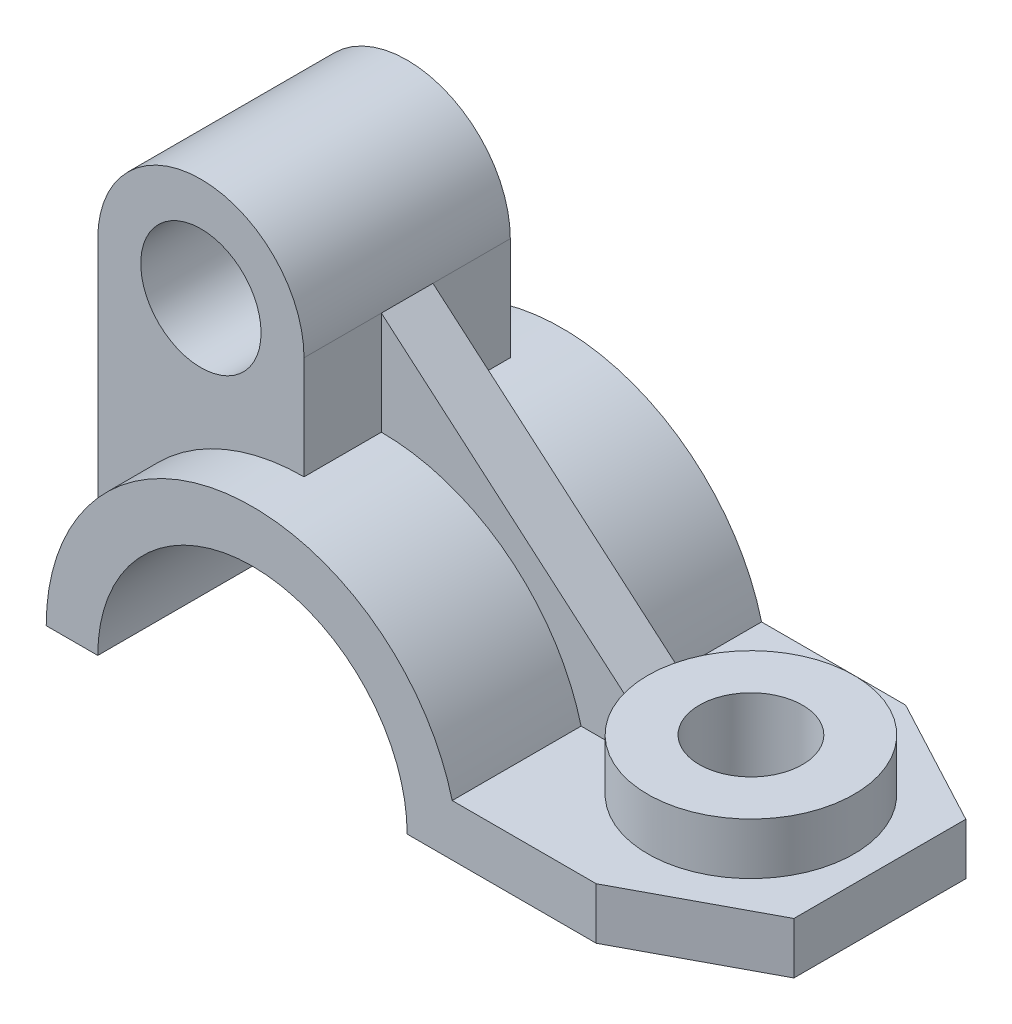
SolidWorks part; units mm, degrees
ref_plane "Front Plane" through (0, 0, 0) normal (0, 0, 1) x (1, 0, 0)
ref_plane "Top Plane" through (0, 0, 0) normal (0, 1, 0) x (1, 0, 0)
ref_plane "Right Plane" through (0, 0, 0) normal (1, 0, 0) x (0, 0, -1)
sketch "Sketch1" plane through (0, 0, 0) normal (0, 0, 1) x (1, 0, 0)
  line L0 (24, 0) -> (55, 0)
  line L1 (55, 0) -> (55, 6)
  line L2 (55, 6) -> (23.2379, 6)
  line L3 (24, 0) -> (18, 0)
  line L4 (-18, 0) -> (-24, 0)
  line L5 (-24, 0) -> (-24, 36)
  line L6 (0, 36) -> (0, 24)
  arc A0 (23.2379, 6) -> (-24, 0) centre (0, 0) ccw
  arc A1 (18, 0) -> (-18, 0) centre (0, 0) ccw
  circle A2 centre (-12, 36) radius 12
  circle A3 centre (-12, 36) radius 7
  dimension "D1" = 36
  dimension "D2" = 48
  dimension "D5" = 36
  dimension "D6" = 24
  dimension "D7" = 14
  dimension "D3" = 55
  dimension "D4" = 6
extrude "Boss-Extrude1" add sketch "Sketch1" along normal mid plane 36 contours A1 L3 L0 L1 L2 A0 L4 region at (21, 0.8257, 0)
extrude "Boss-Extrude2" add sketch "Sketch1<3>" along normal mid plane 24 contours A2 L5 A0 L6 | A2 A3 region at (-16.4261, 21.3196, 0) region at (-12, 47.6606, 0)
sketch "Sketch1<3>" plane through (0, 0, 0) normal (0, 0, 1) x (1, 0, 0) same geometry as "Sketch1"
sketch "Sketch2" plane through (0, 6, 0) normal (0, 1, 0) x (1, 0, 0)
  circle A0 centre (40, 0) radius 12
  dimension "D1" = 24
  dimension "D3" = 40
extrude "Boss-Extrude3" add sketch "Sketch2" along normal blind 6
sketch "Sketch3" plane through (0, 0, 0) normal (0, 0, 1) x (1, 0, 0)
  line L0 (0, 36) -> (28, 12)
  line L1 (0, 36) -> (0, 24) construction
  dimension "D1" = 12
rib "Rib1" sketch "Sketch3" sketch "Sketch3" thickness 6 extrusion direction parallel to sketch draft on no parameters "D1"=6
chamfer "Chamfer1" distance 8 distance2 15 1 edges at (55, 3, 18) first distance on face at (55, 3, 0)
chamfer "Chamfer2" distance 15 distance2 8 1 edges at (55, 3, -18) first distance on face at (17.7658, 8.4681, -18)
hole_wizard "Ø12.0mm Dowel Hole1" positions "3DSketch1" profile "Sketch5" hole size "Ø12.0" standard "ANSI Metric"
sketch3d "3DSketch1"
  line L0 (40, 12, 0) -> (40, 6, 0) construction
  point P0 (40, 12, 0)
sketch "Sketch5" plane through (40, 12, 0) normal (1, 0, 0) x (0, 0, 1)
  line L0 (0, 0) -> (0, 33.6052)
  line L1 (0, 33.6052) -> (6, 30)
  line L2 (6, 30) -> (6, 0)
  line L5 (6, 0) -> (0, 0)
  line L10 (0, 33.6052) -> (-6, 30) construction
  line L11 (0, -6.35) -> (0, 107.95) construction
  dimension "Hole Dia." = 12
  dimension "Hole Depth" = 30
  dimension "Drill Angle" = 118
